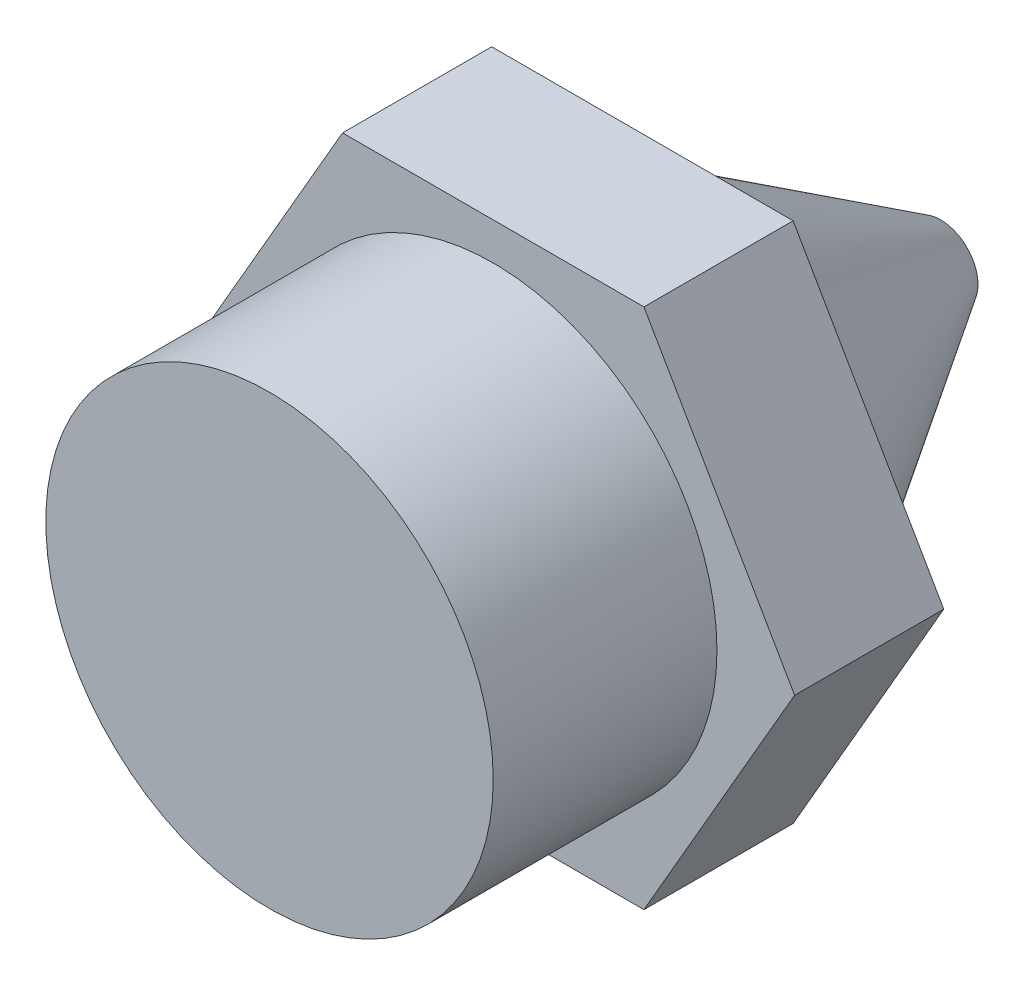
SolidWorks part; units mm, degrees
ref_plane "Plan de face" through (0, 0, 0) normal (0, 0, 1) x (1, 0, 0)
ref_plane "Plan de dessus" through (0, 0, 0) normal (0, 1, 0) x (1, 0, 0)
ref_plane "Plan de droite" through (0, 0, 0) normal (1, 0, 0) x (0, 0, -1)
sketch "Esquisse1" plane through (0, 0, 0) normal (0, 0, 1) x (1, 0, 0)
  line L1 (4.0415, 0) -> (2.0207, 3.5)
  line L2 (2.0207, 3.5) -> (-2.0207, 3.5)
  line L3 (-2.0207, 3.5) -> (-4.0415, 0)
  line L4 (-4.0415, 0) -> (-2.0207, -3.5)
  line L5 (-2.0207, -3.5) -> (2.0207, -3.5)
  line L6 (2.0207, -3.5) -> (4.0415, 0)
  circle A0 centre (0, 0) radius 3.5 construction
  dimension "D1" = 7
extrude "Boss.-Extru.1" add sketch "Esquisse1" along normal blind 9 contours L3 L4 L5 L6 L1 L2
sketch "Esquisse2" plane through (0, 0, 9) normal (0, 0, 1) x (1, 0, 0)
  line L1 (-9.4849, 6.2226) -> (10.1391, 6.2226)
  line L2 (-9.4849, 6.2226) -> (-9.4849, -9.3115)
  line L3 (-9.4849, -9.3115) -> (10.1391, -9.3115)
  line L4 (10.1391, 6.2226) -> (10.1391, -9.3115)
  circle A0 centre (0, 0) radius 3
  dimension "D1" = 6
extrude "Enlèv. mat.-Extru.1" cut sketch "Esquisse2" against normal blind 3
cosmetic thread "Représentation de filetage1" parameters "D1"=3, "D2"=4.891
sketch "Esquisse3" plane through (0, 0, 0) normal (0, 0, -1) x (-1, 0, 0)
  line L1 (5.6434, -6.9413) -> (-5.6238, -6.9413)
  line L2 (5.6434, -6.9413) -> (5.6434, 7.0198)
  line L3 (5.6434, 7.0198) -> (-5.6238, 7.0198)
  line L4 (-5.6238, -6.9413) -> (-5.6238, 7.0198)
  circle A0 centre (0, 0) radius 3
  dimension "D1" = 6
extrude "Enlèv. mat.-Extru.2" cut sketch "Esquisse3" against normal blind 4
chamfer "Chanfrein1" distance 4 angle 32 1 edges at (-3, 0, 0) first distance on face at (-3, 0, 4)
